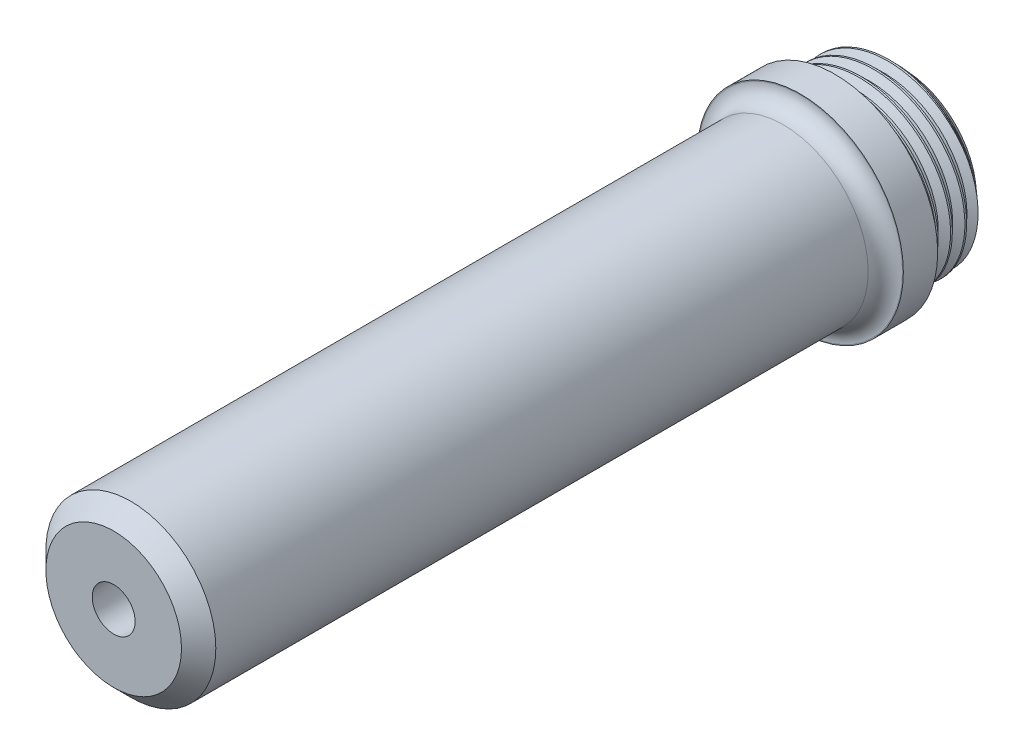
SolidWorks part; units mm, degrees
material "Plain Carbon Steel"
ref_plane "Front Plane" through (0, 0, 0) normal (0, 0, 1) x (1, 0, 0)
ref_plane "Top Plane" through (0, 0, 0) normal (0, 1, 0) x (1, 0, 0)
ref_plane "Right Plane" through (0, 0, 0) normal (1, 0, 0) x (0, 0, -1)
sketch "Sketch1" plane through (0, 0, 0) normal (0, 0, 1) x (1, 0, 0)
  circle A0 centre (0, 0) radius 7.62
  dimension "D1" = 15.24
extrude "Boss-Extrude1" add sketch "Sketch1" along normal blind 2.54
sketch "Sketch2" plane through (0, 0, 0) normal (0, 0, -1) x (-1, 0, 0)
  circle A0 centre (0, 0) radius 6.6675
  dimension "D1" = 13.335
extrude "Boss-Extrude2" add sketch "Sketch2" along normal blind 5.08
sketch "Sketch8" plane through (0, 0, 2.54) normal (0, 0, 1) x (1, 0, 0)
  circle A0 centre (0, 0) radius 6.2865
  dimension "D1" = 12.573
extrude "Boss-Extrude3" add sketch "Sketch8" along normal blind 50.8
thread "Thread1" pitch 1.0583 method cut profile "Thread Profile1" start angle 0, offset 0, length 5.461, pitch 1.0583, diameter 13.335
ref_plane "Plane1" through (6.6675, 0, -5.08) normal (0, -1, 0) x (1, 0, 0)
sketch "Thread Profile1" plane through (6.6675, 0, -5.08) normal (0, -1, 0) x (1, 0, 0)
  line L0 (0, 0) -> (0, 1.0583) construction
  line L11 (0, 0) -> (0, 0.926)
  line L12 (0, 0.926) -> (-0.5728, 0.5953)
  line L13 (-0.5728, 0.5953) -> (-0.5728, 0.3307)
  line L15 (-0.5728, 0.3307) -> (0, 0)
  line L17 (-0.5728, 0.463) -> (0, 0.463) construction
  point P2 (0, 0)
  dimension "Pitch" = 1.0583
  dimension "Profile_Angle" = 60
  dimension "Profile_Land" = 0.2646
  dimension "Profile_Height" = 0.5728
sketch "Sketch6" plane through (0, 0, 0) normal (0, 1, 0) x (1, 0, 0)
  line L0 (0, 0) -> (0, 5.08) construction
  line L1 (6.6675, 5.08) -> (-6.6675, 5.08) construction
  line L2 (4.699, 5.715) -> (7.239, 3.429)
  line L3 (7.239, 3.429) -> (7.239, 5.715)
  line L4 (7.239, 5.715) -> (4.699, 5.715)
  dimension "D1" = 4.699
  dimension "D2" = 2.54
  dimension "D3" = 2.286
  dimension "D4" = 0.635
revolve "Cut-Revolve1" cut sketch "Sketch6" angle 360 about L0
chamfer "Chamfer1" distance 1.27 angle 45 1 edges at (6.2865, 0, 53.34)
sketch "Sketch7" plane through (0, 0, 53.34) normal (0, 0, 1) x (1, 0, 0)
  circle A1 centre (0, 0) radius 1.5875
  dimension "D1" = 3.175
extrude "Cut-Extrude1" cut sketch "Sketch7" against normal through all draft 3 draft outward yes
fillet "Fillet1" radius 1.27 1 edges at (6.2865, 0, 2.54)
